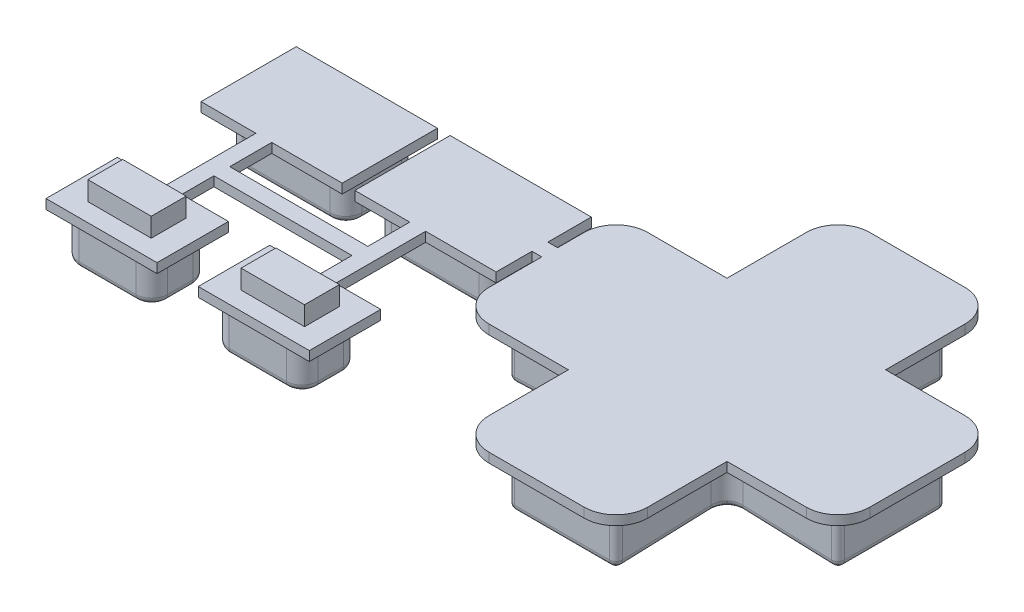
SolidWorks part; units mm, degrees
ref_plane "前视基准面" through (0, 0, 0) normal (0, 0, 1) x (1, 0, 0)
ref_plane "上视基准面" through (0, 0, 0) normal (0, 1, 0) x (1, 0, 0)
ref_plane "右视基准面" through (0, 0, 0) normal (1, 0, 0) x (0, 0, -1)
sketch "草图1" plane through (0, 0, 0) normal (0, 1, 0) x (1, 0, 0)
  line L32 (-10.3556, -1.581) -> (-15.3556, -1.581)
  line L33 (-10.3556, -6.581) -> (-10.3556, -1.581)
  line L34 (-2.3556, -8.581) -> (-8.3556, -8.581)
  line L35 (-0.3556, -1.581) -> (-0.3556, -6.581)
  line L36 (4.6444, -1.581) -> (-0.3556, -1.581)
  line L37 (6.6444, 6.419) -> (6.6444, 0.419)
  line L38 (-0.3556, 8.419) -> (4.6444, 8.419)
  line L39 (-0.3556, 13.419) -> (-0.3556, 8.419)
  line L40 (-8.3556, 15.419) -> (-2.3556, 15.419)
  line L41 (-10.3556, 8.419) -> (-10.3556, 13.419)
  line L42 (-15.3556, 8.419) -> (-10.3556, 8.419)
  line L43 (-17.3556, 0.419) -> (-17.3556, 6.419)
  arc A24 (-17.3556, 0.419) -> (-15.3556, -1.581) centre (-15.3556, 0.419) ccw
  arc A26 (-10.3556, -6.581) -> (-8.3556, -8.581) centre (-8.3556, -6.581) ccw
  arc A27 (-2.3556, -8.581) -> (-0.3556, -6.581) centre (-2.3556, -6.581) ccw
  arc A29 (4.6444, -1.581) -> (6.6444, 0.419) centre (4.6444, 0.419) ccw
  arc A30 (6.6444, 6.419) -> (4.6444, 8.419) centre (4.6444, 6.419) ccw
  arc A32 (-0.3556, 13.419) -> (-2.3556, 15.419) centre (-2.3556, 13.419) ccw
  arc A33 (-8.3556, 15.419) -> (-10.3556, 13.419) centre (-8.3556, 13.419) ccw
  arc A35 (-15.3556, 8.419) -> (-17.3556, 6.419) centre (-15.3556, 6.419) ccw
extrude "凸台-拉伸1" add sketch "草图1" along normal blind 0.6
sketch "草图2" plane through (0, 0, 0) normal (0, -1, 0) x (1, 0, 0)
  line L24 (-15.7556, -0.419) -> (-15.7556, -6.419)
  line L25 (-15.3556, -6.819) -> (-8.7556, -6.819)
  line L26 (-8.7556, -6.819) -> (-8.7556, -13.419)
  line L27 (-8.3556, -13.819) -> (-2.3556, -13.819)
  line L28 (-1.9556, -13.419) -> (-1.9556, -6.819)
  line L29 (-1.9556, -6.819) -> (4.6444, -6.819)
  line L30 (5.0444, -6.419) -> (5.0444, -0.419)
  line L31 (4.6444, -0.019) -> (-1.9556, -0.019)
  line L32 (-1.9556, -0.019) -> (-1.9556, 6.581)
  line L33 (-2.3556, 6.981) -> (-8.3556, 6.981)
  line L34 (-8.7556, 6.581) -> (-8.7556, -0.019)
  line L35 (-8.7556, -0.019) -> (-15.3556, -0.019)
  line L36 (-15.7556, -0.419) -> (-15.7556, -6.419)
  line L37 (-15.3556, -6.819) -> (-8.7556, -6.819)
  line L38 (-8.7556, -6.819) -> (-8.7556, -13.419)
  line L39 (-8.3556, -13.819) -> (-2.3556, -13.819)
  line L40 (-1.9556, -13.419) -> (-1.9556, -6.819)
  line L41 (-1.9556, -6.819) -> (4.6444, -6.819)
  line L42 (5.0444, -6.419) -> (5.0444, -0.419)
  line L43 (4.6444, -0.019) -> (-1.9556, -0.019)
  line L44 (-1.9556, -0.019) -> (-1.9556, 6.581)
  line L45 (-2.3556, 6.981) -> (-8.3556, 6.981)
  line L46 (-8.7556, 6.581) -> (-8.7556, -0.019)
  line L47 (-8.7556, -0.019) -> (-15.3556, -0.019)
  arc A16 (-15.3556, -0.019) -> (-15.7556, -0.419) centre (-15.3556, -0.419) ccw
  arc A17 (-15.7556, -6.419) -> (-15.3556, -6.819) centre (-15.3556, -6.419) ccw
  arc A18 (-8.7556, -13.419) -> (-8.3556, -13.819) centre (-8.3556, -13.419) ccw
  arc A19 (-2.3556, -13.819) -> (-1.9556, -13.419) centre (-2.3556, -13.419) ccw
  arc A20 (4.6444, -6.819) -> (5.0444, -6.419) centre (4.6444, -6.419) ccw
  arc A21 (5.0444, -0.419) -> (4.6444, -0.019) centre (4.6444, -0.419) ccw
  arc A22 (-1.9556, 6.581) -> (-2.3556, 6.981) centre (-2.3556, 6.581) ccw
  arc A23 (-8.3556, 6.981) -> (-8.7556, 6.581) centre (-8.3556, 6.581) ccw
  arc A24 (-15.3556, -0.019) -> (-15.7556, -0.419) centre (-15.3556, -0.419) ccw
  arc A25 (-15.7556, -6.419) -> (-15.3556, -6.819) centre (-15.3556, -6.419) ccw
  arc A26 (-8.7556, -13.419) -> (-8.3556, -13.819) centre (-8.3556, -13.419) ccw
  arc A27 (-2.3556, -13.819) -> (-1.9556, -13.419) centre (-2.3556, -13.419) ccw
  arc A28 (4.6444, -6.819) -> (5.0444, -6.419) centre (4.6444, -6.419) ccw
  arc A29 (5.0444, -0.419) -> (4.6444, -0.019) centre (4.6444, -0.419) ccw
  arc A30 (-1.9556, 6.581) -> (-2.3556, 6.981) centre (-2.3556, 6.581) ccw
  arc A31 (-8.3556, 6.981) -> (-8.7556, 6.581) centre (-8.3556, 6.581) ccw
  dimension "D1" = 1.6
extrude "凸台-拉伸2" add sketch "草图2" along normal blind 3.5
fillet "圆角1" radius 1 4 edges at (-8.7556, -1.75, -0.019) (-8.7556, -1.75, -6.819) (-1.9556, -1.75, -6.819) (-1.9556, -1.75, -0.019)
sketch "草图3" plane through (0, 0, 0) normal (0, -1, 0) x (1, 0, 0)
  line L0 (-10.3556, 1.581) -> (-10.3556, 6.581) construction
  line L1 (-36.573, -1.4829) -> (-27.673, -1.4829)
  line L2 (-36.573, -1.4829) -> (-36.573, -7.4829)
  line L3 (-36.573, -7.4829) -> (-27.673, -7.4829)
  line L4 (-27.673, -1.4829) -> (-27.673, -7.4829)
  line L5 (-26.873, -1.4829) -> (-17.973, -1.4829)
  line L6 (-26.873, -1.4829) -> (-26.873, -7.4829)
  line L7 (-26.873, -7.4829) -> (-17.973, -7.4829)
  line L8 (-17.973, -1.4829) -> (-17.973, -7.4829)
  line L9 (-36.1688, 8.696) -> (-29.1688, 8.696)
  line L10 (-36.1688, 8.696) -> (-36.1688, 4.196)
  line L11 (-36.1688, 4.196) -> (-29.1688, 4.196)
  line L12 (-29.1688, 8.696) -> (-29.1688, 4.196)
  line L13 (-26.5688, 8.696) -> (-19.5688, 8.696)
  line L14 (-26.5688, 8.696) -> (-26.5688, 4.196)
  line L15 (-26.5688, 4.196) -> (-19.5688, 4.196)
  line L16 (-19.5688, 8.696) -> (-19.5688, 4.196)
  line L17 (-15.3556, 1.581) -> (-10.3556, 1.581) construction
  line L18 (-17.3556, -6.419) -> (-17.3556, -0.419) construction
  line L19 (-10.3556, -8.419) -> (-15.3556, -8.419) construction
  point P16 (-36.573, -7.4829)
  point P17 (-36.1688, 4.196)
  point P20 (0, 0)
  point P22 (-15.5959, 2.8035)
  point P26 (0, 0)
  dimension "D1" = 6
  dimension "D2" = 8.9
  dimension "D3" = 7
  dimension "D4" = 4.5
  dimension "D5" = 2.6
  dimension "D6" = 0.8
  dimension "D7" = 9.2131
  dimension "D8" = 2.615
  dimension "D9" = 0.6174
  dimension "D10" = 0.936
extrude "凸台-拉伸3" add sketch "草图3" against normal blind 0.6 separate body
sketch "草图4" plane through (0, 0, 0) normal (0, -1, 0) x (1, 0, 0)
  line L1 (-33.1166, 4.7185) -> (-32.1166, 4.7185)
  line L2 (-33.1166, 4.7185) -> (-33.1166, -1.6561)
  line L3 (-33.1166, -1.6561) -> (-32.1166, -1.6561)
  line L4 (-32.1166, 4.7185) -> (-32.1166, -1.6561)
  line L7 (-23.4153, 4.8891) -> (-22.4153, 4.8891)
  line L8 (-23.4153, 4.8891) -> (-23.4153, -1.7621)
  line L9 (-23.4153, -1.7621) -> (-22.4153, -1.7621)
  line L10 (-22.4153, 4.8891) -> (-22.4153, -1.7621)
  point P4 (-33.123, 4.7185)
  point P5 (-23.423, 4.196)
  point P6 (-32.1166, -1.6561)
  point P7 (0, 0)
  point P12 (-23.423, 4.8891)
  point P13 (0, 0)
  point P14 (-22.4153, -1.7621)
  point P16 (-33.123, 4.196)
  point P17 (0, 0)
  point P18 (0, 0)
  point P19 (-33.123, -1.4829)
  point P20 (0, 0)
  dimension "D1" = 1
  dimension "D2" = 1
extrude "凸台-拉伸4" add sketch "草图4" against normal blind 0.6 separate body
sketch "草图5" plane through (0, 0, 0) normal (0, -1, 0) x (1, 0, 0)
  line L0 (-32.1166, -1.6561) -> (-32.1166, 4.7185) construction
  line L1 (-32.1166, 2.1635) -> (-23.4153, 2.1635)
  line L2 (-32.1166, 2.1635) -> (-32.1166, 1.1635)
  line L3 (-32.1166, 1.1635) -> (-23.4153, 1.1635)
  line L4 (-23.4153, 2.1635) -> (-23.4153, 1.1635)
  line L5 (-23.4153, 4.8891) -> (-23.4153, -1.7621) construction
  line L6 (-17.973, -7.4829) -> (-17.973, -1.4829) construction
  line L7 (-17.973, -3.7438) -> (-17.3556, -3.7438)
  line L8 (-17.973, -3.7438) -> (-17.973, -4.7438)
  line L9 (-17.973, -4.7438) -> (-17.3556, -4.7438)
  line L10 (-17.3556, -3.7438) -> (-17.3556, -4.7438)
  line L11 (-17.3556, -6.419) -> (-17.3556, -0.419) construction
  dimension "D1" = 1
  dimension "D2" = 1
extrude "凸台-拉伸5" add sketch "草图5" against normal blind 0.6
sketch "草图6" plane through (0, 0, 0) normal (0, -1, 0) x (1, 0, 0)
  line L0 (-36.1688, 8.696) -> (-36.1688, 4.196) construction
  line L1 (-35.4979, 8.3012) -> (-29.8979, 8.3012)
  line L2 (-35.4979, 8.3012) -> (-35.4979, 4.7012)
  line L3 (-35.4979, 4.7012) -> (-29.8979, 4.7012)
  line L4 (-29.8979, 8.3012) -> (-29.8979, 4.7012)
  line L5 (-26.0167, 8.3012) -> (-20.4167, 8.3012)
  line L6 (-26.0167, 8.3012) -> (-26.0167, 4.7012)
  line L7 (-26.0167, 4.7012) -> (-20.4167, 4.7012)
  line L8 (-20.4167, 8.3012) -> (-20.4167, 4.7012)
  line L9 (-29.1688, 8.696) -> (-36.1688, 8.696) construction
  line L10 (-26.5688, 8.696) -> (-26.5688, 4.196) construction
  line L11 (-27.673, -1.4829) -> (-36.573, -1.4829) construction
  line L12 (-35.743, -2.2829) -> (-28.243, -2.2829)
  line L13 (-35.743, -2.2829) -> (-35.743, -6.7829)
  line L14 (-35.743, -6.7829) -> (-28.243, -6.7829)
  line L15 (-28.243, -2.2829) -> (-28.243, -6.7829)
  line L16 (-26.363, -2.2829) -> (-18.863, -2.2829)
  line L17 (-26.363, -2.2829) -> (-26.363, -6.7829)
  line L18 (-26.363, -6.7829) -> (-18.863, -6.7829)
  line L19 (-18.863, -2.2829) -> (-18.863, -6.7829)
  line L20 (-36.573, -1.4829) -> (-36.573, -7.4829) construction
  dimension "D1" = 5.6
  dimension "D2" = 0.6709
  dimension "D3" = 3.6
  dimension "D4" = 0.3948
  dimension "D5" = 0.552
  dimension "D6" = 7.5
  dimension "D7" = 4.5
  dimension "D8" = 0.8
  dimension "D9" = 0.83
  dimension "D10" = 1.88
extrude "凸台-拉伸6" add sketch "草图6" along normal blind 2.6
fillet "圆角2" radius 1 16 edges at (-26.363, -1.3, -6.7829) (-18.863, -1.3, -6.7829) (-18.863, -1.3, -2.2829) (-26.363, -1.3, -2.2829) (-28.243, -1.3, -2.2829) (-35.743, -1.3, -2.2829) (-35.743, -1.3, -6.7829) (-28.243, -1.3, -6.7829) (-20.4167, -1.3, 4.7012) (-26.0167, -1.3, 4.7012) (-20.4167, -1.3, 8.3012) (-26.0167, -1.3, 8.3012) (-35.4979, -1.3, 8.3012) (-29.8979, -1.3, 8.3012) (-29.8979, -1.3, 4.7012) (-35.4979, -1.3, 4.7012)
sketch "草图7" plane through (0, -3.5, 0) normal (0, -1, 0) x (1, 0, 0)
  line L0 (-2.3556, 6.981) -> (-8.3556, 6.981) construction
  line L1 (-15.7556, 6.981) -> (5.0444, 6.981)
  line L2 (-15.7556, 6.981) -> (-15.7556, -13.819)
  line L3 (-15.7556, -13.819) -> (5.0444, -13.819)
  line L4 (5.0444, 6.981) -> (5.0444, -13.819)
  line L5 (-15.7556, -0.419) -> (-15.7556, -6.419) construction
  line L6 (-8.3556, -13.819) -> (-2.3556, -13.819) construction
  line L7 (5.0444, -6.419) -> (5.0444, -0.419) construction
  point P4 (0, 0)
extrude "切除-拉伸1" cut sketch "草图7" against normal blind 0.3 draft 88
fillet "圆角3" radius 0.4 68 edges at (-15.6385, -3.4959, -0.1361) (-12.5556, -3.3883, -0.019) (-9.3729, -3.2771, 0.0571) (-7.1648, -3.2, -3.419) (-9.3729, -3.2771, -6.8951) (-12.5556, -3.3883, -6.819) (-15.6385, -3.4959, -6.7018) (-15.7556, -3.5, -3.419) (4.9272, -3.4959, -6.7018) (1.8444, -3.3883, -6.819) (-1.3383, -3.2771, -6.8951) (-3.5465, -3.2, -3.419) (-1.3383, -3.2771, 0.0571) (1.8444, -3.3883, -0.019) (4.9272, -3.4959, -0.1361) (5.0444, -3.5, -3.419) (-8.6385, -3.4959, -13.7018) (-8.7556, -3.3883, -10.619) (-8.8317, -3.2771, -7.4363) (-8.1066, -3.2329, -6.17) (-5.3556, -3.2, -5.2281) (-2.6046, -3.2329, -6.17) (-1.8795, -3.2771, -7.4363) (-1.9556, -3.3883, -10.619) (-2.0728, -3.4959, -13.7018) (-5.3556, -3.5, -13.819) (-8.6385, -3.4959, 6.8639) (-5.3556, -3.5, 6.981) (-2.0728, -3.4959, 6.8639) (-1.9556, -3.3883, 3.781) (-1.8795, -3.2771, 0.5983) (-2.6046, -3.2329, -0.668) (-5.3556, -3.2, -1.6099) (-8.1066, -3.2329, -0.668) (-8.8317, -3.2771, 0.5983) (-8.7556, -3.3883, 3.781) (-25.7238, -2.6, 4.9941) (-26.0167, -2.6, 6.5012) (-25.7238, -2.6, 8.0083) (-23.2167, -2.6, 8.3012) (-20.7096, -2.6, 8.0083) (-20.4167, -2.6, 6.5012) (-20.7096, -2.6, 4.9941) (-23.2167, -2.6, 4.7012) (-30.1908, -2.6, 8.0083) (-29.8979, -2.6, 6.5012) (-30.1908, -2.6, 4.9941) (-32.6979, -2.6, 4.7012) (-35.205, -2.6, 4.9941) (-35.4979, -2.6, 6.5012) (-35.205, -2.6, 8.0083) (-32.6979, -2.6, 8.3012) (-26.0701, -2.6, -2.5758) (-22.613, -2.6, -2.2829) (-19.1559, -2.6, -2.5758) (-18.863, -2.6, -4.5329) (-19.1559, -2.6, -6.4901) (-22.613, -2.6, -6.7829) (-26.0701, -2.6, -6.4901) (-26.363, -2.6, -4.5329) (-28.5359, -2.6, -6.4901) (-31.993, -2.6, -6.7829) (-35.4501, -2.6, -6.4901) (-35.743, -2.6, -4.5329) (-35.4501, -2.6, -2.5758) (-31.993, -2.6, -2.2829) (-28.5359, -2.6, -2.5758) (-28.243, -2.6, -4.5329)
sketch "草图8" plane through (0, 0.6, 0) normal (0, 1, 0) x (1, 0, 0)
  line L1 (-34.6856, -5.3444) -> (-30.6856, -5.3444)
  line L2 (-34.6856, -5.3444) -> (-34.6856, -7.5444)
  line L3 (-34.6856, -7.5444) -> (-30.6856, -7.5444)
  line L4 (-30.6856, -5.3444) -> (-30.6856, -7.5444)
  line L5 (-34.6856, -5.3444) -> (-30.6856, -7.5444) construction
  line L6 (-34.6856, -7.5444) -> (-30.6856, -5.3444) construction
  line L7 (-25.0234, -5.3444) -> (-21.0234, -5.3444)
  line L8 (-25.0234, -5.3444) -> (-25.0234, -7.5444)
  line L9 (-25.0234, -7.5444) -> (-21.0234, -7.5444)
  line L10 (-21.0234, -5.3444) -> (-21.0234, -7.5444)
  line L11 (-25.0234, -5.3444) -> (-21.0234, -7.5444) construction
  line L12 (-25.0234, -7.5444) -> (-21.0234, -5.3444) construction
  point P0 (-32.6856, -6.4444)
  point P5 (-23.0234, -6.4444)
  dimension "D1" = 4
  dimension "D2" = 2.2
extrude "凸台-拉伸7" add sketch "草图8" along normal blind 1.2
